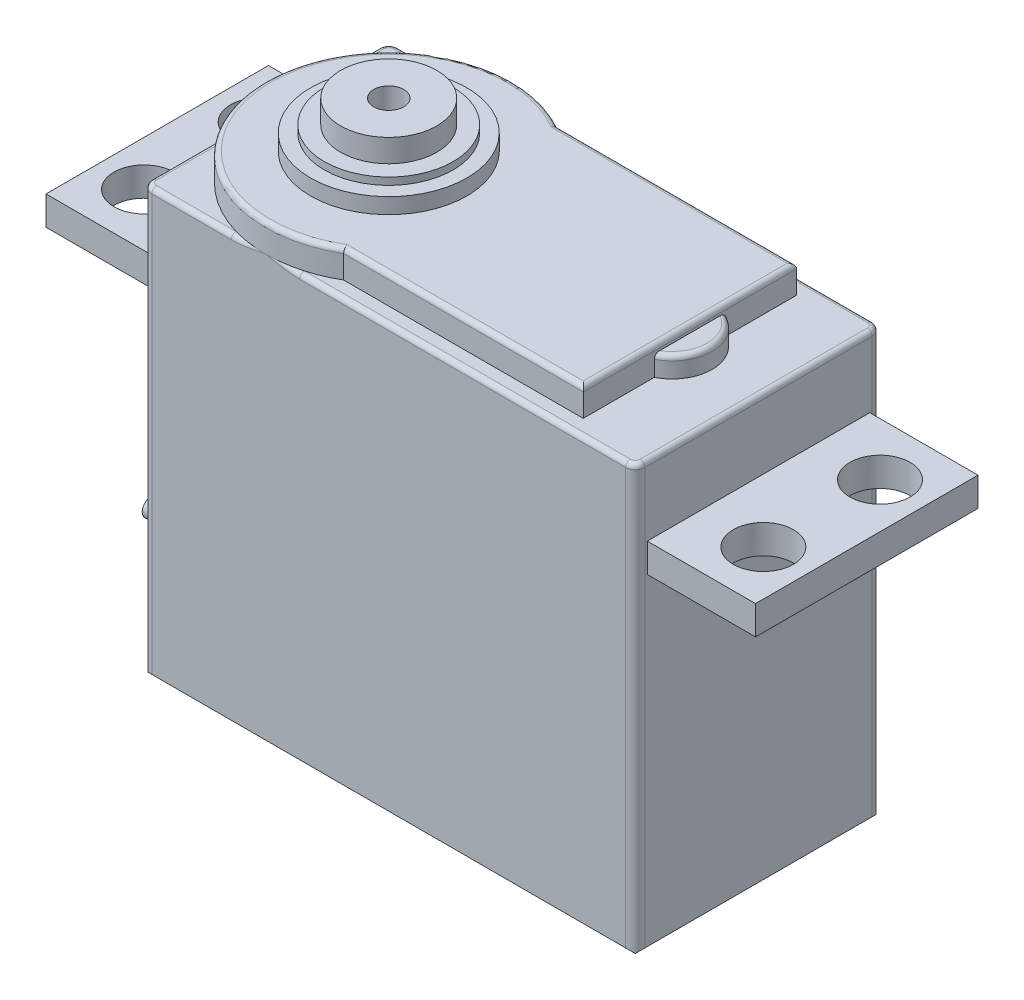
SolidWorks part; units mm, degrees
material "PE High Density"
ref_plane "Front Plane" through (0, 0, 0) normal (0, 0, 1) x (1, 0, 0)
ref_plane "Top Plane" through (0, 0, 0) normal (0, 1, 0) x (1, 0, 0)
ref_plane "Right Plane" through (0, 0, 0) normal (1, 0, 0) x (0, 0, -1)
sketch "Sketch1" plane through (0, 0, 0) normal (0, 1, 0) x (1, 0, 0)
  line L1 (-20.5, -10.25) -> (20.5, -10.25)
  line L2 (-20.5, -10.25) -> (-20.5, 10.25)
  line L3 (-20.5, 10.25) -> (20.5, 10.25)
  line L4 (20.5, -10.25) -> (20.5, 10.25)
  line L5 (-20.5, -10.25) -> (20.5, 10.25) construction
  line L6 (-20.5, 10.25) -> (20.5, -10.25) construction
  point P0 (0, 0)
  dimension "D1" = 41
  dimension "D2" = 20.5
extrude "Boss-Extrude1" add sketch "Sketch1" along normal blind 37
sketch "Sketch2" plane through (0, 37, 0) normal (0, 1, 0) x (1, 0, 0)
  line L0 (-20.5, 10.25) -> (-20.5, -10.25) construction
  line L1 (20.5, -10.25) -> (20.5, 10.25) construction
  line L2 (-5.122, -8.875) -> (14.8, -8.875)
  line L4 (-5.122, 8.875) -> (14.8, 8.875)
  line L5 (14.8, -8.875) -> (14.8, -2.9672)
  line L9 (14.8, 2.9672) -> (14.8, 8.875)
  arc A0 (-5.122, 8.875) -> (-5.122, -8.875) centre (-10.25, 0) ccw
  arc A1 (14.8, -2.9672) -> (14.8, 2.9672) centre (13.3208, 0) ccw
  point P5 (4.4919, 0)
  dimension "D1" = 10.25
  dimension "D2" = 17.75
  dimension "D3" = 5.7
extrude "Boss-Extrude2" add sketch "Sketch2" along normal blind 2.3
sketch "Sketch3" plane through (0, 39.3, 0) normal (0, 1, 0) x (1, 0, 0)
  circle A0 centre (-10.25, 0) radius 6.5
  dimension "D1" = 13
extrude "Boss-Extrude3" add sketch "Sketch3" along normal blind 1.3
sketch "Sketch4" plane through (0, 40.6, 0) normal (0, 1, 0) x (1, 0, 0)
  circle A0 centre (-10.25, 0) radius 5.35
  dimension "D1" = 10.7
extrude "Boss-Extrude4" add sketch "Sketch4" along normal blind 0.6
sketch "Sketch5" plane through (0, 39.3, 0) normal (0, 1, 0) x (1, 0, 0)
  line L0 (14.8, 2.9672) -> (14.8, -2.9672)
  arc A0 (14.8, -2.9672) -> (14.8, 2.9672) centre (13.3208, 0) ccw construction
  arc A1 (14.8, -2.9672) -> (14.8, 2.9672) centre (13.3208, 0) ccw
extrude "Cut-Extrude1" cut sketch "Sketch5" against normal blind 0.6
sketch "Sketch6" plane through (0, 41.2, 0) normal (0, 1, 0) x (1, 0, 0)
  circle A0 centre (-10.25, 0) radius 4
  dimension "D1" = 8
extrude "Boss-Extrude5" add sketch "Sketch6" along normal blind 1.9
chamfer "Chamfer1" distance 2 angle 45 4 edges at (-20.5, 0, 0) (0, 0, -10.25) (20.5, 0, 0) (0, 0, 10.25)
fillet "Fillet2" radius 0.8 4 edges at (-20.5, 19.5, -10.25) (-20.5, 19.5, 10.25) (20.5, 19.5, -10.25) (20.5, 19.5, 10.25)
sketch "Sketch7" plane through (-20.5, 0, 0) normal (-1, 0, 0) x (0, 0, 1)
  line L1 (-9.25, 31.2) -> (9.25, 31.2)
  line L2 (-9.25, 31.2) -> (-9.25, 28.8)
  line L3 (-9.25, 28.8) -> (9.25, 28.8)
  line L4 (9.25, 31.2) -> (9.25, 28.8)
  line L6 (-9.45, 37) -> (0, 37) construction
  line L9 (-10.25, 37) -> (-10.25, 2) construction
  dimension "D1" = 5.8
  dimension "D2" = 2.4
  dimension "D3" = 18.5
  dimension "D4" = 1
extrude "Boss-Extrude6" add sketch "Sketch7" along normal blind 9
ref_plane "Plane1" through (0, 0, 0) normal (-1, 0, 0) x (0, 0, 1)
sketch "Sketch12" plane through (0, 43.1, 0) normal (0, 1, 0) x (1, 0, 0)
  circle A0 centre (-10.25, 0) radius 1.25
  dimension "D1" = 2.5
extrude "Cut-Extrude4" cut sketch "Sketch12" against normal blind 4
fillet "Fillet5" radius 0.4 5 edges at (16.6363, 38.7, 0) (14.8, 39.3, 0) (4.839, 39.3, -8.875) (-20.5, 39.3, 0) (4.839, 39.3, 8.875)
fillet "Fillet7" radius 0.4 11 edges at (20.2657, 37, 10.0157) (4.725, 37, 10.25) (-14.975, 37, 10.25) (-20.2657, 37, 10.0157) (-20.5, 37, 4.725) (-20.5, 37, -4.725) (-20.2657, 37, -10.0157) (-14.975, 37, -10.25) (4.725, 37, -10.25) (20.2657, 37, -10.0157) (20.5, 37, 0)
sketch "Sketch13" plane through (-20.5, 0, 0) normal (-1, 0, 0) x (0, 0, 1)
  line L0 (8.25, 0) -> (-8.25, 0) construction
  line L1 (-3.5, 3.2) -> (3.5, 3.2)
  line L2 (-3.5, 3.2) -> (-3.5, 7.4)
  line L3 (-3.5, 7.4) -> (3.5, 7.4)
  line L4 (3.5, 3.2) -> (3.5, 7.4)
  line L5 (-3.5, 3.2) -> (3.5, 7.4) construction
  line L6 (-3.5, 7.4) -> (3.5, 3.2) construction
  point P0 (0, 5.3)
  dimension "D1" = 7
  dimension "D2" = 4.2
  dimension "D3" = 3.2
extrude "Boss-Extrude8" add sketch "Sketch13" along normal blind 1
sketch "Sketch14" plane through (-21.5, 0, 0) normal (-1, 0, 0) x (0, 0, 1)
  line L9 (3.15, 3.55) -> (3.15, 7.05)
  line L10 (3.15, 7.05) -> (-3.15, 7.05)
  line L11 (-3.15, 7.05) -> (-3.15, 3.55)
  line L12 (-3.15, 3.55) -> (3.15, 3.55)
  line L13 (3.15, 3.55) -> (3.15, 7.05)
  line L14 (3.15, 7.05) -> (-3.15, 7.05)
  line L15 (-3.15, 7.05) -> (-3.15, 3.55)
  line L16 (-3.15, 3.55) -> (3.15, 3.55)
  dimension "D1" = 0.35
extrude "Boss-Extrude9" add sketch "Sketch14" along normal blind 4 draft 5 contours L14 L15 L16 L13
sketch "Sketch15" plane through (-25.5, 0, 0) normal (-1, 0, 0) x (0, 0, 1)
  line L0 (-2.8, 3.9) -> (2.8, 3.9) construction
  circle A0 centre (-1.5, 5.3) radius 0.75
  circle A1 centre (0, 5.3) radius 0.75
  circle A2 centre (1.5, 5.3) radius 0.75
  dimension "D1" = 1.5
  dimension "D2" = 1.5
  dimension "D3" = 1.5
  dimension "D4" = 1.4
extrude "Boss-Extrude12" add sketch "Sketch15" along normal blind 3 separate body contours A0 | A1 | A2 region at (-25.5, 5.3, -1.5) region at (-25.5, 5.3, 1.5) region at (-25.5, 5.3, 0)
sketch "Croquis1" plane through (0, 37, 0) normal (0, 1, 0) x (1, 0, 0)
sketch "Croquis2" plane through (0, 31.2, 0) normal (0, 1, 0) x (1, 0, 0)
  line L0 (0, 0) -> (-25.75, 0) construction
  line L1 (-25.75, 0) -> (-25.75, 4.85) construction
  line L2 (-25.75, 0) -> (-25.75, -4.85) construction
  circle A0 centre (-25.75, 4.85) radius 2.5
  circle A1 centre (-25.75, -4.85) radius 2.5
extrude "Cortar-Extruir1" cut sketch "Croquis2" against normal blind 10
mirror "Simetría1" about plane through (0, 0, 0) normal (-1, 0, 0) of "Boss-Extrude6"
mirror "Simetría2" about plane through (0, 0, 0) normal (-1, 0, 0) of "Cortar-Extruir1"
